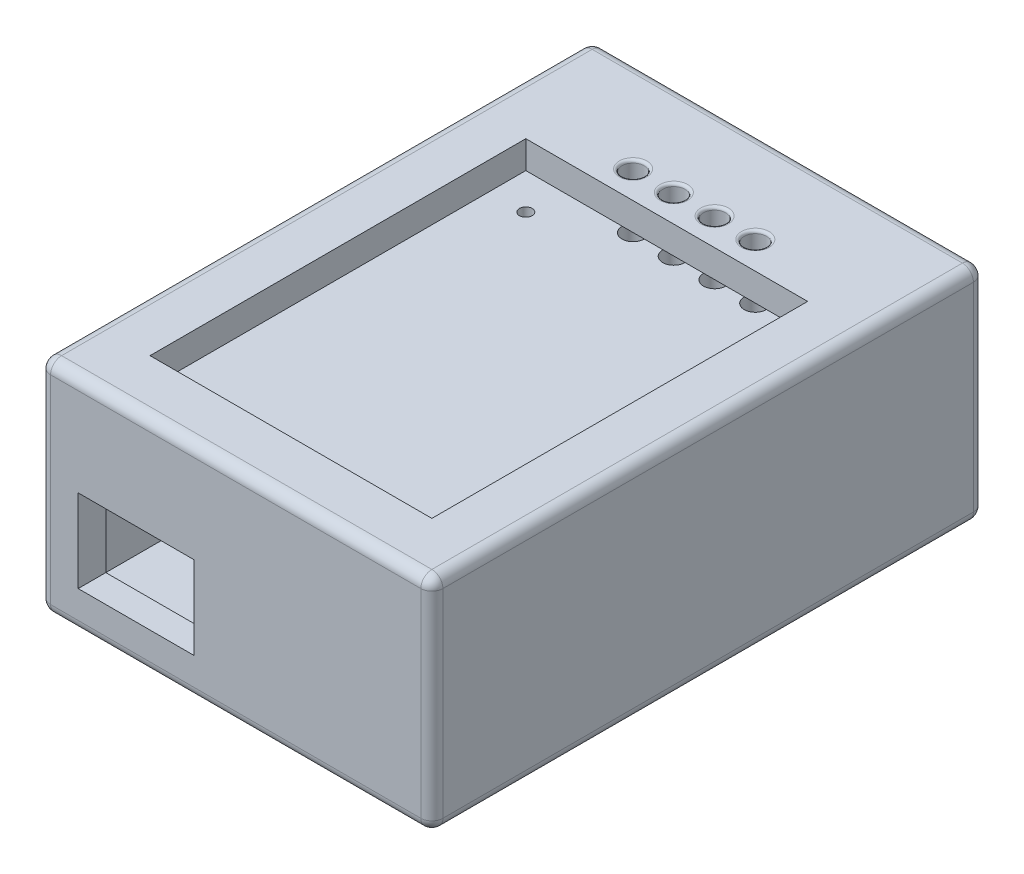
SolidWorks part; units mm, degrees
ref_plane "Front Plane" through (0, 0, 0) normal (0, 0, 1) x (1, 0, 0)
ref_plane "Top Plane" through (0, 0, 0) normal (0, 1, 0) x (1, 0, 0)
ref_plane "Right Plane" through (0, 0, 0) normal (1, 0, 0) x (0, 0, -1)
sketch "Sketch1" plane through (0, 0, 0) normal (0, 1, 0) x (1, 0, 0)
  line L1 (-35.5, 50) -> (35.5, 50)
  line L2 (-35.5, 50) -> (-35.5, -50)
  line L3 (-35.5, -50) -> (35.5, -50)
  line L4 (35.5, 50) -> (35.5, -50)
  line L5 (-35.5, 50) -> (35.5, -50) construction
  line L6 (-35.5, -50) -> (35.5, 50) construction
  point P0 (0, 0)
  dimension "D1" = 71
  dimension "D2" = 100
extrude "Boss-Extrude1" add sketch "Sketch1" along normal blind 30
shell "Shell3" thickness 5 removed face at (0, 30, 0)
sketch "Sketch3" plane through (0, 30, 0) normal (0, 1, 0) x (1, 0, 0)
  line L1 (-35.5, 50) -> (35.5, 50)
  line L2 (-35.5, 50) -> (-35.5, -50)
  line L3 (-35.5, -50) -> (35.5, -50)
  line L4 (35.5, 50) -> (35.5, -50)
extrude "Boss-Extrude2" add sketch "Sketch3" against normal blind 5
sketch "Sketch4" plane through (0, 30, 0) normal (0, 1, 0) x (1, 0, 0)
  line L0 (-35.5, 50) -> (-35.5, -50) construction
  line L1 (-25.5, 28) -> (25.5, 28)
  line L2 (-25.5, 28) -> (-25.5, -40)
  line L3 (-25.5, -40) -> (25.5, -40)
  line L4 (25.5, 28) -> (25.5, -40)
  line L5 (35.5, -50) -> (35.5, 50) construction
  line L6 (-35.5, -50) -> (35.5, -50) construction
  dimension "D1" = 10
  dimension "D2" = 10
  dimension "D3" = 10
  dimension "D4" = 68
extrude "Cut-Extrude2" cut sketch "Sketch4" against normal blind 5
extrude "Boss-Extrude3" add sketch "Sketch1<2>" against normal blind 10
sketch "Sketch1<2>" plane through (0, 0, 0) normal (0, 1, 0) x (1, 0, 0) same geometry as "Sketch1"
sketch "Sketch10" plane through (0, -10, 0) normal (0, -1, 0) x (1, 0, 0)
  line L0 (35.5, 50) -> (35.5, -50) construction
  line L1 (30.5, 45) -> (-30.5, 45)
  line L2 (30.5, 45) -> (30.5, -45)
  line L3 (30.5, -45) -> (-30.5, -45)
  line L4 (-30.5, 45) -> (-30.5, -45)
  line L5 (-35.5, 50) -> (35.5, 50) construction
  line L6 (-35.5, -50) -> (-35.5, 50) construction
  line L7 (35.5, -50) -> (-35.5, -50) construction
  dimension "D1" = 5
  dimension "D2" = 5
  dimension "D3" = 5
  dimension "D4" = 5
extrude "Cut-Extrude6" cut sketch "Sketch10" against normal blind 20
extrude "Boss-Extrude4" add sketch "Sketch10<2>" against normal blind 5
sketch "Sketch10<2>" plane through (0, -10, 0) normal (0, -1, 0) x (1, 0, 0) same geometry as "Sketch10"
sketch "Sketch12" plane through (35.5, 0, 0) normal (1, 0, 0) x (0, 0, -1)
  line L0 (-50, 30) -> (-50, -10) construction
  line L1 (-50, 20) -> (50, 20)
  line L2 (-50, 20) -> (-50, 15)
  line L3 (-50, 15) -> (50, 15)
  line L4 (50, 20) -> (50, 15)
  line L5 (50, 30) -> (50, -10) construction
  line L6 (-50, -10) -> (50, -10) construction
  line L7 (-50, 30) -> (50, 30) construction
  dimension "D1" = 25
  dimension "D2" = 10
extrude "Boss-Extrude5" add sketch "Sketch12" against normal blind 71
sketch "Sketch5" plane through (0, 30, 0) normal (0, 1, 0) x (1, 0, 0)
  line L0 (-45.9354, 32.97) -> (52.8119, 32.97) construction
  line L1 (-35.5, 50) -> (-35.5, -50) construction
  line L2 (35.5, 50) -> (-35.5, 50) construction
  line L3 (-11.055, 46.4277) -> (-11.055, 27.5388) construction
  line L5 (-3.685, 46.4277) -> (-3.685, 25.3574) construction
  line L6 (3.685, 46.4277) -> (3.685, 25.3574) construction
  line L7 (11.055, 46.4277) -> (11.055, 25.3574) construction
  circle A0 centre (-11.055, 32.97) radius 2
  circle A1 centre (-3.685, 32.97) radius 2
  circle A2 centre (3.685, 32.97) radius 2
  circle A3 centre (11.055, 32.97) radius 2
  dimension "D1" = 17.03
  dimension "D2" = 24.445
  dimension "D3" = 7.37
  dimension "D4" = 7.37
  dimension "D5" = 7.37
extrude "Cut-Extrude3" cut sketch "Sketch5" against normal blind 25
sketch "Sketch13" plane through (0, 20, 0) normal (0, 1, 0) x (1, 0, 0)
  line L0 (-29.1566, 26.5) -> (29.2941, 26.5) construction
  line L1 (-24, 27.0248) -> (-24, -44.6288) construction
  line L2 (-29.1566, -34.5) -> (28.3314, -34.5) construction
  line L3 (24, 27.0248) -> (24, -44.6288) construction
  line L4 (-25.5, 28) -> (-25.5, -40) construction
  line L5 (25.5, 28) -> (-25.5, 28) construction
  line L6 (25.5, -40) -> (25.5, 28) construction
  line L7 (-25.5, -40) -> (25.5, -40) construction
  circle A0 centre (-24, 26.5) radius 1.15
  circle A1 centre (24, 26.5) radius 1.15
  circle A2 centre (24, -34.5) radius 1.15
  circle A3 centre (-24, -34.5) radius 1.15
  point P24 (-24, -34.6688)
  point P25 (-24, -44.6288)
  dimension "D1" = 1.5
  dimension "D2" = 1.5
  dimension "D3" = 1.5
  dimension "D5" = 5.5
extrude "Cut-Extrude7" cut sketch "Sketch13" against normal blind 5 from offset 2
sketch "Sketch14" plane through (0, 0, 50) normal (0, 0, 1) x (1, 0, 0)
  line L0 (-35.5, -10) -> (35.5, -10) construction
  line L1 (-28.5, 12) -> (-7.5, 12)
  line L2 (-28.5, 12) -> (-28.5, -3)
  line L3 (-28.5, -3) -> (-7.5, -3)
  line L4 (-7.5, 12) -> (-7.5, -3)
  line L5 (-35.5, 30) -> (-35.5, -10) construction
  dimension "D1" = 15
  dimension "D2" = 21
  dimension "D3" = 7
  dimension "D4" = 7
extrude "Cut-Extrude8" cut sketch "Sketch14" against normal blind 5
sketch "Sketch15" plane through (0, -10, 0) normal (0, -1, 0) x (1, 0, 0)
  line L0 (28, -55.7688) -> (28, 53.8434) construction
  line L1 (39.3339, 28.5) -> (-45.1102, 28.5) construction
  line L2 (-28, -53.8434) -> (-28, 55.0812) construction
  line L3 (40.4341, -36.04) -> (-43.3223, -36.04) construction
  line L4 (35.5, 50) -> (35.5, -50) construction
  line L5 (-35.5, -50) -> (-35.5, 50) construction
  line L6 (-35.5, 50) -> (35.5, 50) construction
  line L7 (35.5, -50) -> (-35.5, -50) construction
  circle A0 centre (28, -36.04) radius 1.15
  circle A1 centre (-28, -36.04) radius 1.15
  circle A2 centre (28, 28.5) radius 1.15
  circle A3 centre (-28, 28.5) radius 1.15
  dimension "D1" = 7.5
  dimension "D2" = 7.5
  dimension "D3" = 21.5
  dimension "D4" = 13.96
extrude "Cut-Extrude9" cut sketch "Sketch15" against normal blind 3 from offset 2 offset against normal yes
sketch "Sketch16" plane through (0, 20, 0) normal (0, 1, 0) x (1, 0, 0)
  line L0 (-25.5, -40) -> (25.5, -40) construction
  line L1 (-14, -30) -> (14, -30)
  line L2 (-14, -30) -> (-14, -40)
  line L3 (-14, -40) -> (14, -40)
  line L4 (14, -30) -> (14, -40)
  line L5 (0, 53.7059) -> (0, -55.6313) construction
  dimension "D1" = 28
  dimension "D2" = 10
extrude "Cut-Extrude10" cut sketch "Sketch16" against normal blind 10
fillet "Fillet1" radius 2 11 edges at (0, 30, -50) (35.5, 10, 50) (35.5, 30, 0) (35.5, 10, -50) (0, -10, -50) (0, -10, 50) (35.5, -10, 0) (-35.5, 10, -50) (-35.5, 30, 0) (-35.5, 10, 50) (-35.5, -10, 0)
fillet "Fillet2" radius 2 3 edges at (-34.9142, 29.4142, 49.4142) (34.9142, 29.4142, 49.4142) (0, 30, 50)
fillet "Fillet5" radius 0.5 4 edges at (11.055, 30, -30.97) (3.685, 30, -30.97) (-3.685, 30, -30.97) (-11.055, 30, -30.97)
